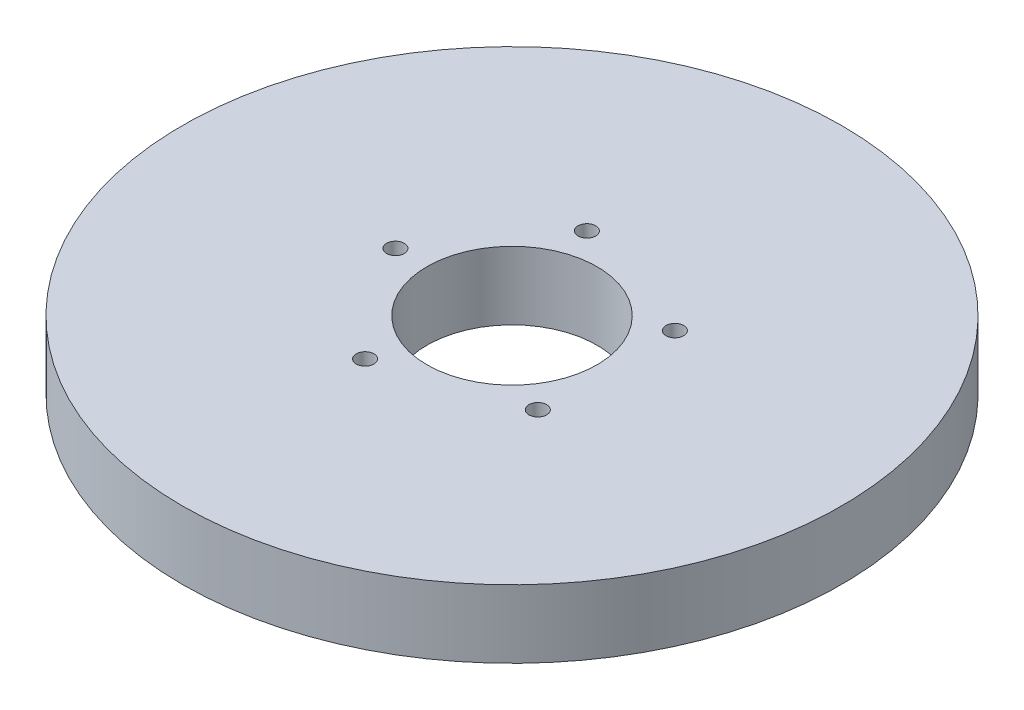
SolidWorks part; units mm, degrees
ref_plane "Front Plane" through (0, 0, 0) normal (0, 0, 1) x (1, 0, 0)
ref_plane "Top Plane" through (0, 0, 0) normal (0, 1, 0) x (1, 0, 0)
ref_plane "Right Plane" through (0, 0, 0) normal (1, 0, 0) x (0, 0, -1)
sketch "Sketch1" plane through (0, 0, 0) normal (0, 1, 0) x (1, 0, 0)
  circle A0 centre (0, 0) radius 77.5
  dimension "FLANGE_OD" = 155
extrude "Boss-Extrude1" add sketch "Sketch1" along normal blind 16
sketch "Sketch2" plane through (0, 0, 0) normal (0, 1, 0) x (1, 0, 0)
  circle A0 centre (0, 0) radius 20
  dimension "BORE_D" = 40
extrude "Cut-Extrude1" cut sketch "Sketch2" along normal through all
sketch "Sketch3" plane through (0, 16, 0) normal (0, 1, 0) x (1, 0, 0)
  circle A0 centre (0, 0) radius 27.4193 construction
  circle A1 centre (-27.4193, 0) radius 2.0861
  dimension "BOLT_D" = 4.1721
  dimension "BOLT_PCD" = 54.8385
extrude "Cut-Extrude2" cut sketch "Sketch3" against normal blind 14.2762
pattern_circular "CirPattern1" count 5 over 360 about axis through (0, 0, 0) along (0, 1, 0) of "Cut-Extrude2"
